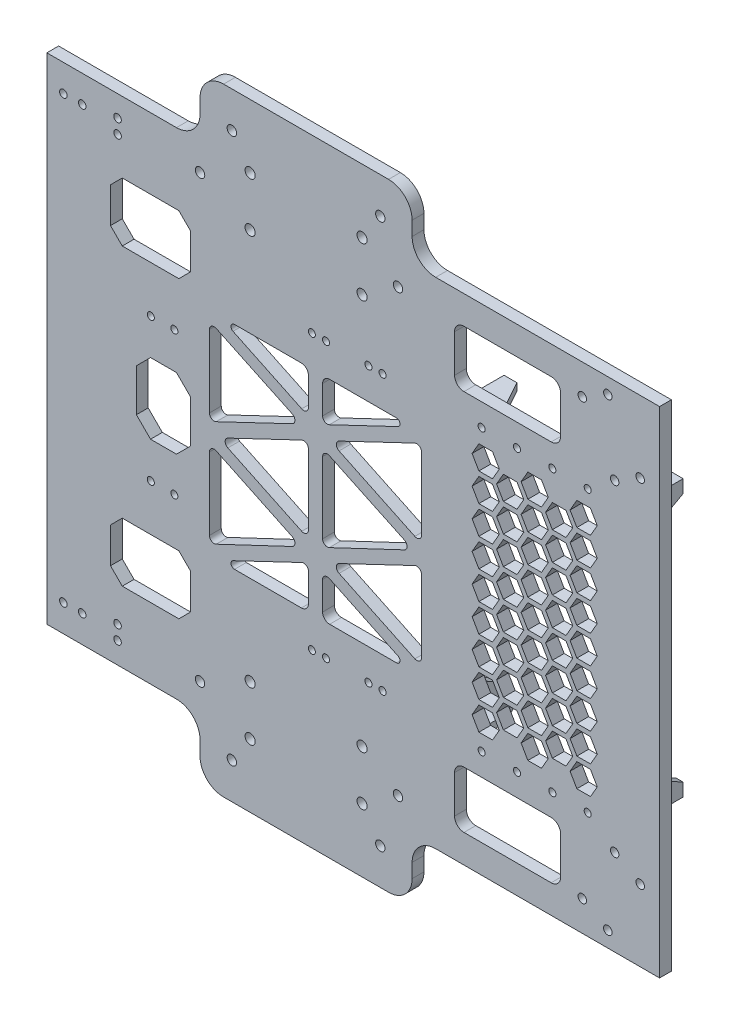
SolidWorks part; units mm, degrees
ref_plane "前视基准面" through (0, 0, 0) normal (0, 0, 1) x (1, 0, 0)
ref_plane "上视基准面" through (0, 0, 0) normal (0, 1, 0) x (1, 0, 0)
ref_plane "右视基准面" through (0, 0, 0) normal (1, 0, 0) x (0, 0, -1)
sketch "草图1" plane through (0, 0, 0) normal (0, 0, 1) x (1, 0, 0)
  line L2 (-130, 105) -> (-130, -105)
  line L3 (-130, -105) -> (-75, -105)
  line L4 (130, 95) -> (130, -95)
  line L5 (126.7518, 102.3765) -> (130, 105) construction
  line L9 (-65, -115) -> (-65, -121)
  line L10 (-55, -131) -> (15, -131)
  line L11 (25, -121) -> (25, -115)
  line L13 (35, -105) -> (120, -105)
  line L14 (126.7518, -102.3765) -> (130, -105) construction
  line L16 (-130, 0) -> (130, 0) construction
  line L17 (35, 105) -> (120, 105)
  line L18 (25, 121) -> (25, 115)
  line L19 (-55, 131) -> (15, 131)
  line L20 (-65, 115) -> (-65, 121)
  line L21 (-130, 105) -> (-75, 105)
  arc A3 (120, -105) -> (130, -95) centre (120, -95) ccw
  arc A8 (-65, -115) -> (-75, -105) centre (-75, -115) ccw
  arc A9 (25, -115) -> (35, -105) centre (35, -115) cw
  arc A10 (-55, -131) -> (-65, -121) centre (-55, -121) cw
  arc A11 (15, -131) -> (25, -121) centre (15, -121) ccw
  arc A12 (15, 131) -> (25, 121) centre (15, 121) cw
  arc A13 (-55, 131) -> (-65, 121) centre (-55, 121) ccw
  arc A14 (25, 115) -> (35, 105) centre (35, 115) ccw
  arc A15 (-65, 115) -> (-75, 105) centre (-75, 115) cw
  arc A16 (120, 105) -> (130, 95) centre (120, 95) cw
  point P0 (0, 0)
  point P40 (25, -105)
  point P45 (25, 105)
  dimension "D3" = 65
  dimension "D4" = 10
  dimension "D5" = 105
  dimension "D7" = 10
  dimension "D8" = 10
  dimension "D10" = 10
  dimension "D12" = 10
  dimension "D13" = 105
  dimension "D18" = 90
  dimension "D19" = 6
extrude "凸台-拉伸1" add sketch "草图1" along normal blind 5
sketch "草图4" plane through (0, 0, 0) normal (0, 0, -1) x (-1, 0, 0)
  line L0 (-39, -47.5) -> (-39, -58.5)
  line L1 (-39, -58.5) -> (-50, -58.5)
  line L2 (-50, -58.5) -> (-50, -55.5)
  line L3 (-50, -55.5) -> (-42, -55.5)
  line L4 (-42, -55.5) -> (-42, -47.5)
  line L5 (-42, -47.5) -> (-39, -47.5)
  line L6 (-130, 0) -> (-25.5592, 0) construction
  line L7 (-130, -95) -> (-130, 95) construction
  line L10 (-130, -95) -> (-130, 95) construction
  dimension "D1" = 11
  dimension "D2" = 11
  dimension "D3" = 3
  dimension "D4" = 3
  dimension "D5" = 80
  dimension "D7" = 55.5
extrude "凸台-拉伸2" add sketch "草图4" along normal blind 20
sketch "草图5" plane through (0, -58.5, 0) normal (0, -1, 0) x (1, 0, 0)
  line L0 (50, -10) -> (44.5, -20)
  line L1 (50, -20) -> (50, 0) construction
  line L2 (50, -20) -> (39, -20) construction
  line L3 (44.5, -20) -> (50, -20)
  line L4 (50, -20) -> (50, -10)
  dimension "D1" = 10
  dimension "D2" = 5.5
extrude "切除-拉伸3" cut sketch "草图5" against normal blind 10
sketch "草图6" plane through (39, 0, 0) normal (-1, 0, 0) x (0, 0, 1)
  line L0 (-20, -53) -> (-10, -47.5)
  line L1 (-20, -58.5) -> (-20, -47.5) construction
  line L2 (-20, -47.5) -> (0, -47.5) construction
  line L3 (-10, -47.5) -> (-20, -47.5)
  line L4 (-20, -47.5) -> (-20, -53)
  dimension "D1" = 10
  dimension "D2" = 5.5
extrude "切除-拉伸4" cut sketch "草图6" against normal blind 10
ref_plane "基准面2" through (77, 0, 0) normal (1, 0, 0) x (0, 0, -1)
mirror "镜向1" about plane through (77, 0, 0) normal (1, 0, 0) of "凸台-拉伸2", "切除-拉伸4", "切除-拉伸3"
mirror "镜向2" about plane through (0, 0, 0) normal (0, 1, 0) of "镜向1"
sketch "草图7" plane through (0, 0, 0) normal (0, 0, -1) x (-1, 0, 0)
  line L4 (-112, -55.5) -> (-104, -55.5) construction
  line L5 (-112, 47.5) -> (-112, 55.5) construction
  line L6 (-112, 55.5) -> (-104, 55.5) construction
  line L7 (-92.013, 36) -> (-94.8997, 41)
  line L8 (-94.8997, 41) -> (-100.6732, 41)
  line L9 (-100.6732, 41) -> (-103.56, 36)
  line L10 (-103.56, 36) -> (-100.6732, 31)
  line L11 (-100.6732, 31) -> (-94.8997, 31)
  line L12 (-94.8997, 31) -> (-92.013, 36)
  line L13 (-77.0019, 36) -> (-97.7865, 36) construction
  line L14 (-74.1151, 31) -> (-71.2284, 36)
  line L15 (-71.2284, 36) -> (-74.1151, 41)
  line L16 (-74.1151, 41) -> (-79.8886, 41)
  line L17 (-79.8886, 41) -> (-82.7754, 36)
  line L18 (-82.7754, 36) -> (-79.8886, 31)
  line L19 (-79.8886, 31) -> (-74.1151, 31)
  line L20 (-92.013, 24) -> (-94.8997, 29)
  line L21 (-93.1677, 30) -> (-90.2809, 25)
  line L22 (-90.2809, 25) -> (-84.5074, 25)
  line L23 (-84.5074, 25) -> (-81.6207, 30)
  line L24 (-81.6207, 30) -> (-84.5074, 35)
  line L25 (-84.5074, 35) -> (-90.2809, 35)
  line L26 (-90.2809, 35) -> (-93.1677, 30)
  line L27 (-84.5074, 37) -> (-81.6207, 42)
  line L28 (-81.6207, 42) -> (-84.5074, 47)
  line L29 (-84.5074, 47) -> (-90.2809, 47)
  line L30 (-90.2809, 47) -> (-93.1677, 42)
  line L31 (-93.1677, 42) -> (-90.2809, 37)
  line L32 (-90.2809, 37) -> (-84.5074, 37)
  line L33 (-79.8886, 43) -> (-74.1151, 43)
  line L34 (-74.1151, 43) -> (-71.2284, 48)
  line L35 (-71.2284, 48) -> (-74.1151, 53)
  line L36 (-74.1151, 53) -> (-79.8886, 53)
  line L37 (-79.8886, 53) -> (-82.7754, 48)
  line L38 (-82.7754, 48) -> (-79.8886, 43)
  line L39 (-94.8997, 43) -> (-92.013, 48)
  line L40 (-92.013, 48) -> (-94.8997, 53)
  line L41 (-94.8997, 53) -> (-100.6732, 53)
  line L42 (-100.6732, 53) -> (-103.56, 48)
  line L43 (-103.56, 48) -> (-100.6732, 43)
  line L44 (-100.6732, 43) -> (-94.8997, 43)
  line L45 (-72.3831, 42) -> (-69.4963, 37)
  line L46 (-69.4963, 37) -> (-63.7228, 37)
  line L47 (-63.7228, 37) -> (-60.8361, 42)
  line L48 (-60.8361, 42) -> (-63.7228, 47)
  line L49 (-63.7228, 47) -> (-69.4963, 47)
  line L50 (-69.4963, 47) -> (-72.3831, 42)
  line L51 (-94.8997, 29) -> (-100.6732, 29)
  line L52 (-100.6732, 29) -> (-103.56, 24)
  line L53 (-103.56, 24) -> (-100.6732, 19)
  line L54 (-100.6732, 19) -> (-94.8997, 19)
  line L55 (-94.8997, 19) -> (-92.013, 24)
  line L56 (-93.1677, 18) -> (-90.2809, 13)
  line L57 (-90.2809, 13) -> (-84.5074, 13)
  line L58 (-84.5074, 13) -> (-81.6207, 18)
  line L59 (-81.6207, 18) -> (-84.5074, 23)
  line L60 (-84.5074, 23) -> (-90.2809, 23)
  line L61 (-90.2809, 23) -> (-93.1677, 18)
  line L62 (-74.1151, 19) -> (-71.2284, 24)
  line L63 (-71.2284, 24) -> (-74.1151, 29)
  line L64 (-74.1151, 29) -> (-79.8886, 29)
  line L65 (-79.8886, 29) -> (-82.7754, 24)
  line L66 (-82.7754, 24) -> (-79.8886, 19)
  line L67 (-79.8886, 19) -> (-74.1151, 19)
  line L68 (-72.3831, 30) -> (-69.4963, 25)
  line L69 (-69.4963, 25) -> (-63.7228, 25)
  line L70 (-63.7228, 25) -> (-60.8361, 30)
  line L71 (-60.8361, 30) -> (-63.7228, 35)
  line L72 (-63.7228, 35) -> (-69.4963, 35)
  line L73 (-69.4963, 35) -> (-72.3831, 30)
  line L74 (-92.013, 12) -> (-94.8997, 17)
  line L75 (-94.8997, 17) -> (-100.6732, 17)
  line L76 (-100.6732, 17) -> (-103.56, 12)
  line L77 (-103.56, 12) -> (-100.6732, 7)
  line L78 (-100.6732, 7) -> (-94.8997, 7)
  line L79 (-94.8997, 7) -> (-92.013, 12)
  line L80 (-93.1677, 6) -> (-90.2809, 1)
  line L81 (-90.2809, 1) -> (-84.5074, 1)
  line L82 (-84.5074, 1) -> (-81.6207, 6)
  line L83 (-81.6207, 6) -> (-84.5074, 11)
  line L84 (-84.5074, 11) -> (-90.2809, 11)
  line L85 (-90.2809, 11) -> (-93.1677, 6)
  line L86 (-74.1151, 7) -> (-71.2284, 12)
  line L87 (-71.2284, 12) -> (-74.1151, 17)
  line L88 (-74.1151, 17) -> (-79.8886, 17)
  line L89 (-79.8886, 17) -> (-82.7754, 12)
  line L90 (-82.7754, 12) -> (-79.8886, 7)
  line L91 (-79.8886, 7) -> (-74.1151, 7)
  line L92 (-72.3831, 18) -> (-69.4963, 13)
  line L93 (-69.4963, 13) -> (-63.7228, 13)
  line L94 (-63.7228, 13) -> (-60.8361, 18)
  line L95 (-60.8361, 18) -> (-63.7228, 23)
  line L96 (-63.7228, 23) -> (-69.4963, 23)
  line L97 (-69.4963, 23) -> (-72.3831, 18)
  line L98 (-92.013, 0) -> (-94.8997, 5)
  line L99 (-94.8997, 5) -> (-100.6732, 5)
  line L100 (-100.6732, 5) -> (-103.56, 0)
  line L101 (-103.56, 0) -> (-100.6732, -5)
  line L102 (-100.6732, -5) -> (-94.8997, -5)
  line L103 (-94.8997, -5) -> (-92.013, 0)
  line L104 (-93.1677, -6) -> (-90.2809, -11)
  line L105 (-90.2809, -11) -> (-84.5074, -11)
  line L106 (-84.5074, -11) -> (-81.6207, -6)
  line L107 (-81.6207, -6) -> (-84.5074, -1)
  line L108 (-84.5074, -1) -> (-90.2809, -1)
  line L109 (-90.2809, -1) -> (-93.1677, -6)
  line L110 (-74.1151, -5) -> (-71.2284, 0)
  line L111 (-71.2284, 0) -> (-74.1151, 5)
  line L112 (-74.1151, 5) -> (-79.8886, 5)
  line L113 (-79.8886, 5) -> (-82.7754, 0)
  line L114 (-82.7754, 0) -> (-79.8886, -5)
  line L115 (-79.8886, -5) -> (-74.1151, -5)
  line L116 (-72.3831, 6) -> (-69.4963, 1)
  line L117 (-69.4963, 1) -> (-63.7228, 1)
  line L118 (-63.7228, 1) -> (-60.8361, 6)
  line L119 (-60.8361, 6) -> (-63.7228, 11)
  line L120 (-63.7228, 11) -> (-69.4963, 11)
  line L121 (-69.4963, 11) -> (-72.3831, 6)
  line L122 (-92.013, -12) -> (-94.8997, -7)
  line L123 (-94.8997, -7) -> (-100.6732, -7)
  line L124 (-100.6732, -7) -> (-103.56, -12)
  line L125 (-103.56, -12) -> (-100.6732, -17)
  line L126 (-100.6732, -17) -> (-94.8997, -17)
  line L127 (-94.8997, -17) -> (-92.013, -12)
  line L128 (-93.1677, -18) -> (-90.2809, -23)
  line L129 (-90.2809, -23) -> (-84.5074, -23)
  line L130 (-84.5074, -23) -> (-81.6207, -18)
  line L131 (-81.6207, -18) -> (-84.5074, -13)
  line L132 (-84.5074, -13) -> (-90.2809, -13)
  line L133 (-90.2809, -13) -> (-93.1677, -18)
  line L134 (-74.1151, -17) -> (-71.2284, -12)
  line L135 (-71.2284, -12) -> (-74.1151, -7)
  line L136 (-74.1151, -7) -> (-79.8886, -7)
  line L137 (-79.8886, -7) -> (-82.7754, -12)
  line L138 (-82.7754, -12) -> (-79.8886, -17)
  line L139 (-79.8886, -17) -> (-74.1151, -17)
  line L140 (-72.3831, -6) -> (-69.4963, -11)
  line L141 (-69.4963, -11) -> (-63.7228, -11)
  line L142 (-63.7228, -11) -> (-60.8361, -6)
  line L143 (-60.8361, -6) -> (-63.7228, -1)
  line L144 (-63.7228, -1) -> (-69.4963, -1)
  line L145 (-69.4963, -1) -> (-72.3831, -6)
  line L146 (-92.013, -24) -> (-94.8997, -19)
  line L147 (-94.8997, -19) -> (-100.6732, -19)
  line L148 (-100.6732, -19) -> (-103.56, -24)
  line L149 (-103.56, -24) -> (-100.6732, -29)
  line L150 (-100.6732, -29) -> (-94.8997, -29)
  line L151 (-94.8997, -29) -> (-92.013, -24)
  line L152 (-93.1677, -30) -> (-90.2809, -35)
  line L153 (-90.2809, -35) -> (-84.5074, -35)
  line L154 (-84.5074, -35) -> (-81.6207, -30)
  line L155 (-81.6207, -30) -> (-84.5074, -25)
  line L156 (-84.5074, -25) -> (-90.2809, -25)
  line L157 (-90.2809, -25) -> (-93.1677, -30)
  line L158 (-74.1151, -29) -> (-71.2284, -24)
  line L159 (-71.2284, -24) -> (-74.1151, -19)
  line L160 (-74.1151, -19) -> (-79.8886, -19)
  line L161 (-79.8886, -19) -> (-82.7754, -24)
  line L162 (-82.7754, -24) -> (-79.8886, -29)
  line L163 (-79.8886, -29) -> (-74.1151, -29)
  line L164 (-72.3831, -18) -> (-69.4963, -23)
  line L165 (-69.4963, -23) -> (-63.7228, -23)
  line L166 (-63.7228, -23) -> (-60.8361, -18)
  line L167 (-60.8361, -18) -> (-63.7228, -13)
  line L168 (-63.7228, -13) -> (-69.4963, -13)
  line L169 (-69.4963, -13) -> (-72.3831, -18)
  line L170 (-92.013, -36) -> (-94.8997, -31)
  line L171 (-94.8997, -31) -> (-100.6732, -31)
  line L172 (-100.6732, -31) -> (-103.56, -36)
  line L173 (-103.56, -36) -> (-100.6732, -41)
  line L174 (-100.6732, -41) -> (-94.8997, -41)
  line L175 (-94.8997, -41) -> (-92.013, -36)
  line L176 (-93.1677, -42) -> (-90.2809, -47)
  line L177 (-90.2809, -47) -> (-84.5074, -47)
  line L178 (-84.5074, -47) -> (-81.6207, -42)
  line L179 (-81.6207, -42) -> (-84.5074, -37)
  line L180 (-84.5074, -37) -> (-90.2809, -37)
  line L181 (-90.2809, -37) -> (-93.1677, -42)
  line L182 (-74.1151, -41) -> (-71.2284, -36)
  line L183 (-71.2284, -36) -> (-74.1151, -31)
  line L184 (-74.1151, -31) -> (-79.8886, -31)
  line L185 (-79.8886, -31) -> (-82.7754, -36)
  line L186 (-82.7754, -36) -> (-79.8886, -41)
  line L187 (-79.8886, -41) -> (-74.1151, -41)
  line L188 (-72.3831, -30) -> (-69.4963, -35)
  line L189 (-69.4963, -35) -> (-63.7228, -35)
  line L190 (-63.7228, -35) -> (-60.8361, -30)
  line L191 (-60.8361, -30) -> (-63.7228, -25)
  line L192 (-63.7228, -25) -> (-69.4963, -25)
  line L193 (-69.4963, -25) -> (-72.3831, -30)
  line L194 (-92.013, -48) -> (-94.8997, -43)
  line L195 (-94.8997, -43) -> (-100.6732, -43)
  line L196 (-100.6732, -43) -> (-103.56, -48)
  line L197 (-103.56, -48) -> (-100.6732, -53)
  line L198 (-100.6732, -53) -> (-94.8997, -53)
  line L199 (-94.8997, -53) -> (-92.013, -48)
  line L206 (-74.1151, -53) -> (-71.2284, -48)
  line L207 (-71.2284, -48) -> (-74.1151, -43)
  line L208 (-74.1151, -43) -> (-79.8886, -43)
  line L209 (-79.8886, -43) -> (-82.7754, -48)
  line L210 (-82.7754, -48) -> (-79.8886, -53)
  line L211 (-79.8886, -53) -> (-74.1151, -53)
  line L212 (-72.3831, -42) -> (-69.4963, -47)
  line L213 (-69.4963, -47) -> (-63.7228, -47)
  line L214 (-63.7228, -47) -> (-60.8361, -42)
  line L215 (-60.8361, -42) -> (-63.7228, -37)
  line L216 (-63.7228, -37) -> (-69.4963, -37)
  line L217 (-69.4963, -37) -> (-72.3831, -42)
  line L218 (-61.9908, 36) -> (-59.104, 31)
  line L219 (-61.9908, 48) -> (-59.104, 43)
  line L220 (-59.104, 43) -> (-53.3305, 43)
  line L221 (-53.3305, 43) -> (-50.4438, 48)
  line L222 (-50.4438, 48) -> (-53.3305, 53)
  line L223 (-53.3305, 53) -> (-59.104, 53)
  line L224 (-59.104, 53) -> (-61.9908, 48)
  line L225 (-59.104, 31) -> (-53.3305, 31)
  line L226 (-53.3305, 31) -> (-50.4438, 36)
  line L227 (-50.4438, 36) -> (-53.3305, 41)
  line L228 (-53.3305, 41) -> (-59.104, 41)
  line L229 (-59.104, 41) -> (-61.9908, 36)
  line L230 (-61.9908, 24) -> (-59.104, 19)
  line L231 (-59.104, 19) -> (-53.3305, 19)
  line L232 (-53.3305, 19) -> (-50.4438, 24)
  line L233 (-50.4438, 24) -> (-53.3305, 29)
  line L234 (-53.3305, 29) -> (-59.104, 29)
  line L235 (-59.104, 29) -> (-61.9908, 24)
  line L236 (-61.9908, 12) -> (-59.104, 7)
  line L237 (-59.104, 7) -> (-53.3305, 7)
  line L238 (-53.3305, 7) -> (-50.4438, 12)
  line L239 (-50.4438, 12) -> (-53.3305, 17)
  line L240 (-53.3305, 17) -> (-59.104, 17)
  line L241 (-59.104, 17) -> (-61.9908, 12)
  line L242 (-61.9908, 0) -> (-59.104, -5)
  line L243 (-59.104, -5) -> (-53.3305, -5)
  line L244 (-53.3305, -5) -> (-50.4438, 0)
  line L245 (-50.4438, 0) -> (-53.3305, 5)
  line L246 (-53.3305, 5) -> (-59.104, 5)
  line L247 (-59.104, 5) -> (-61.9908, 0)
  line L248 (-61.9908, -12) -> (-59.104, -17)
  line L249 (-59.104, -17) -> (-53.3305, -17)
  line L250 (-53.3305, -17) -> (-50.4438, -12)
  line L251 (-50.4438, -12) -> (-53.3305, -7)
  line L252 (-53.3305, -7) -> (-59.104, -7)
  line L253 (-59.104, -7) -> (-61.9908, -12)
  line L254 (-61.9908, -24) -> (-59.104, -29)
  line L255 (-59.104, -29) -> (-53.3305, -29)
  line L256 (-53.3305, -29) -> (-50.4438, -24)
  line L257 (-50.4438, -24) -> (-53.3305, -19)
  line L258 (-53.3305, -19) -> (-59.104, -19)
  line L259 (-59.104, -19) -> (-61.9908, -24)
  line L260 (-61.9908, -36) -> (-59.104, -41)
  line L261 (-59.104, -41) -> (-53.3305, -41)
  line L262 (-53.3305, -41) -> (-50.4438, -36)
  line L263 (-50.4438, -36) -> (-53.3305, -31)
  line L264 (-53.3305, -31) -> (-59.104, -31)
  line L265 (-59.104, -31) -> (-61.9908, -36)
  line L266 (-61.9908, -48) -> (-59.104, -53)
  line L267 (-59.104, -53) -> (-53.3305, -53)
  line L268 (-53.3305, -53) -> (-50.4438, -48)
  line L269 (-50.4438, -48) -> (-53.3305, -43)
  line L270 (-53.3305, -43) -> (-59.104, -43)
  line L271 (-59.104, -43) -> (-61.9908, -48)
  line L272 (-93.1677, -54) -> (-90.2809, -59) [skipped]
  line L273 (-90.2809, -59) -> (-84.5074, -59) [skipped]
  line L274 (-84.5074, -59) -> (-81.6207, -54) [skipped]
  line L275 (-81.6207, -54) -> (-84.5074, -49) [skipped]
  line L276 (-84.5074, -49) -> (-90.2809, -49) [skipped]
  line L277 (-90.2809, -49) -> (-93.1677, -54) [skipped]
  circle A0 centre (-97.7865, 36) radius 5 construction
  circle A1 centre (-77.0019, 36) radius 5 construction
  circle A2 centre (-87.3942, 30) radius 5 construction
  circle A3 centre (-87.3942, 42) radius 5 construction
  circle A4 centre (-77.0019, 48) radius 5 construction
  circle A5 centre (-97.7865, 48) radius 5 construction
  circle A6 centre (-66.6096, 42) radius 5 construction
  circle A7 centre (-56.2173, 48) radius 5 construction
  point P4 (-87.3942, 37)
  dimension "D1" = 2
  dimension "D3" = 10
  dimension "D4" = 10
  dimension "D5" = 2
  dimension "D7" = 10
  dimension "D11" = 10
  dimension "D14" = 10
  dimension "D15" = 10
  dimension "D20" = 10
  dimension "D2" = 2
  dimension "D6" = 2
  dimension "D8" = 2
  dimension "D9" = 2
  dimension "D10" = 2
  dimension "D12" = 2
  dimension "D13" = 2
  dimension "D16" = 2
  dimension "D17" = 2
  dimension "D19" = 2
  dimension "D21" = 9
  dimension "D22" = 2.5
  dimension "D23" = 2.5
  dimension "D24" = 8.44
  dimension "D18" = 8
extrude "切除-拉伸5" cut sketch "草图7" against normal blind 5
sketch "草图8" plane through (0, 0, 0) normal (0, 0, -1) x (-1, 0, 0)
  line L0 (-75.3677, 120) -> (-75.3677, -120)
  line L1 (-100.0285, 77.2863) -> (-100.0285, -77.2863)
  line L2 (-100.0285, 77.2863) -> (-75.3677, 120)
  line L3 (-100.0285, -77.2863) -> (-75.3677, -120)
  line L4 (-37.1297, 0) -> (-146.8562, 0) construction
  dimension "D1" = 30
  dimension "D2" = 30
  dimension "D3" = 120
  dimension "D4" = 120
sketch "草图9" plane through (0, 0, 0) normal (0, 0, -1) x (-1, 0, 0)
  line L0 (148.8518, 0) -> (-37.1297, 0) construction
  line L1 (-29, 41) -> (-29, 4)
  line L2 (-25, -45) -> (13, -45)
  line L3 (61, -41) -> (61, -4)
  line L4 (57, 45) -> (19, 45)
  line L14 (-29, 41) -> (9.8049, 22.5)
  line L15 (57, 0) -> (19, -18.1163)
  line L16 (130, 105) -> (130, -105) construction
  line L17 (63, 93) -> (118, 93)
  line L18 (63, 93) -> (63, 66)
  line L19 (63, 66) -> (118, 66)
  line L20 (118, 93) -> (118, 66)
  line L21 (75, 105) -> (130, 105) construction
  line L22 (63, -66) -> (118, -66)
  line L23 (118, -93) -> (118, -66)
  line L24 (63, -93) -> (118, -93)
  line L25 (63, -93) -> (63, -66)
  line L26 (-120, 105) -> (-35, 105) construction
  line L27 (-43, 93) -> (-88, 93)
  line L28 (-43, 93) -> (-43, 69)
  line L29 (-43, 69) -> (-88, 69)
  line L30 (-88, 93) -> (-88, 69)
  line L31 (-130, -95) -> (-130, 95) construction
  line L32 (-43, -69) -> (-88, -69)
  line L33 (-88, -93) -> (-88, -69)
  line L34 (-43, -93) -> (-88, -93)
  line L35 (-43, -93) -> (-43, -69)
  line L36 (-25, 45) -> (13, 26.8837)
  line L37 (-25, -45) -> (13, -26.8837)
  line L38 (61, 41) -> (22.0746, 22.5575)
  line L39 (-25.5359, 0) -> (13, -18.258)
  line L40 (57, 45) -> (19, 26.8837)
  line L41 (57, -45) -> (19, -26.8837)
  line L42 (16, 61.4977) -> (16, -60.5731) construction
  line L43 (13, 45) -> (13, 26.8837)
  line L44 (19, 45) -> (19, 26.8837)
  line L45 (13, 18.258) -> (13, -18.258)
  line L46 (9.8049, 22.5) -> (-29, 4)
  line L47 (19, 18.1163) -> (57, 0)
  line L48 (22.0746, 22.5575) -> (61, 4)
  line L49 (13, 18.258) -> (-25.5359, 0)
  line L50 (19, 18.1163) -> (19, -18.1163)
  line L51 (22.0746, -22.5575) -> (61, -41)
  line L52 (9.8049, -22.5) -> (-29, -41)
  line L53 (9.8049, -22.5) -> (-29, -4)
  line L54 (22.0746, -22.5575) -> (61, -4)
  line L55 (13, -26.8837) -> (13, -45)
  line L56 (19, -26.8837) -> (19, -45)
  line L57 (13, 45) -> (-25, 45)
  line L58 (-29, -4) -> (-29, -41)
  line L59 (19, -45) -> (57, -45)
  line L60 (61, 4) -> (61, 41)
  line L61 (-44, 41) -> (-44, -37.8122) construction
  dimension "D1" = 45
  dimension "D2" = 45
  dimension "D3" = 15
  dimension "D4" = 90
  dimension "D5" = 1
  dimension "D7" = 12
  dimension "D8" = 12
  dimension "D9" = 27
  dimension "D10" = 55
  dimension "D11" = 12
  dimension "D12" = 45
  dimension "D13" = 42
  dimension "D14" = 24
  dimension "D21" = 4
  dimension "D22" = 4
  dimension "D23" = 4
  dimension "D24" = 4
  dimension "D26" = 4
  dimension "D27" = 3
  dimension "D28" = 45
extrude "切除-拉伸6" cut sketch "草图9" against normal blind 5 contours L27 L30 L29 L28 | L34 L35 L32 L33 | L4 L44 L40 | L48 L60 L38 | L47 L50 L15 | L54 L51 L3 | L56 L59 L41 | L55 L37 L2 | L53 L58 L52 | L45 L49 L39 | L46 L14 L1 | L43 L57 L36 | L57 L36 L43 region at (16.065, 22.5, 0) region at (-0.3333, -38.9612, 0) region at (-48.0249, -22.5192, 0) region at (-31.6667, 38.9612, 0) region at (-31.6667, 0, 0) region at (65.5, 81, 0) region at (65.5, -81, 0) region at (-0.3333, 38.9612, 0) region at (-48.0249, 22.5192, 0) region at (-0.1547, 0, 0) region at (-31.6667, -38.9612, 0) region at (16.065, -22.5, 0)
fillet "圆角1" radius 4 8 edges at (43, -93, 2.5) (88, -69, 2.5) (43, -69, 2.5) (88, -93, 2.5) (88, 69, 2.5) (43, 69, 2.5) (43, 93, 2.5) (88, 93, 2.5)
fillet "圆角2" radius 1.5 4 edges at (25, -45, 2.5) (-57, -45, 2.5) (25, 45, 2.5) (-57, 45, 2.5)
fillet "圆角3" radius 2 22 edges at (29, -4, 2.5) (29, 4, 2.5) (-13, -18.258, 2.5) (-61, -41, 2.5) (-61, 4, 2.5) (-13, -26.8837, 2.5) (-13, 18.258, 2.5) (-61, -4, 2.5) (-22.0746, -22.5575, 2.5) (25.5359, 0, 2.5) (-22.0746, 22.5575, 2.5) (-61, 41, 2.5) (-19, 26.8837, 2.5) (-19, -26.8837, 2.5) (-19, -18.1163, 2.5) (29, -41, 2.5) (29, 41, 2.5) (-57, 0, 2.5) (-9.8049, -22.5, 2.5) (-13, 26.8837, 2.5) (-9.8049, 22.5, 2.5) (-19, 18.1163, 2.5)
fillet "圆角4" radius 3 4 edges at (-13, -45, 2.5) (-13, 45, 2.5) (-19, -45, 2.5) (-19, 45, 2.5)
sketch "草图12" plane through (0, 0, 0) normal (0, 0, -1) x (-1, 0, 0)
  line L1 (-120, 105) -> (-130, 105)
  line L2 (-120, 105) -> (-120, -105)
  line L3 (-120, -105) -> (-130, -105)
  line L4 (-130, 105) -> (-130, -105)
extrude "凸台-拉伸3" add sketch "草图12" against normal up to surface (5 mm away) up to face at (65.5, 81, 5)
hole_wizard "M3 六角头螺栓的柱形沉头孔1" positions "草图16" profile "草图17" counterbore size "M3" standard "GB" end condition through all
sketch "草图16" plane through (-124.3639, -131.0101, -4.2) normal (0, 0, -1) x (0, 1, 0)
  point P0 (221.0101, 24.3639)
  point P3 (227.0101, 24.3639)
sketch "草图17" plane through (-100, 90, -4.2) normal (1, 0, 0) x (0, 1, 0)
  line L0 (0, 0) -> (0, 9.2)
  line L1 (0, 9.2) -> (1.6, 9.2)
  line L2 (1.6, 9.2) -> (1.6, 1.6)
  line L3 (1.6, 1.6) -> (2.95, 1.6)
  line L4 (2.95, 1.6) -> (2.95, 0)
  line L5 (2.95, 0) -> (0, 0)
  line L6 (0, -6.35) -> (0, 107.95) construction
  dimension "通孔孔直径" = 3.2
  dimension "通孔孔深度" = 9.2
  dimension "柱形沉头孔直径" = 5.9
  dimension "柱形沉头孔深度" = 1.6
sketch "草图10" plane through (0, 0, 0) normal (0, 0, -1) x (-1, 0, 0)
  line L0 (-37.1297, 0) -> (-146.8562, 0) construction
  line L1 (-37.1297, 0) -> (-146.8562, 0) construction
  circle A0 centre (-121.782, 74.6081) radius 1.8 construction
  circle A1 centre (-110.9567, 68.3581) radius 1.8 construction
  circle A2 centre (-108.032, 98.4238) radius 1.8 construction
  circle A3 centre (-97.2067, 92.1738) radius 1.8 construction
  circle A4 centre (-3.75, 104) radius 2.15 construction
  circle A5 centre (-3.75, 104) radius 2.15
  circle A6 centre (-3.75, -104) radius 2.15
  circle A7 centre (115, 93.5) radius 1.6 construction
  circle A8 centre (123, 93.5) radius 1.6 construction
  circle A9 centre (115, 93.5) radius 1.6
  circle A10 centre (123, 93.5) radius 1.6
  circle A11 centre (123, -93.5) radius 1.6
  circle A12 centre (115, -93.5) radius 1.6
  circle A13 centre (100, 96) radius 1.6 construction
  circle A14 centre (100, 90) radius 1.6 construction
  circle A15 centre (-121.782, 74.6081) radius 1.8
  circle A16 centre (-110.9567, 68.3581) radius 1.8
  circle A17 centre (-108.032, 98.4238) radius 1.8
  circle A18 centre (-97.2067, 92.1738) radius 1.8
  circle A41 centre (-97.2067, -92.1738) radius 1.8
  circle A42 centre (-108.032, -98.4238) radius 1.8
  circle A43 centre (-110.9567, -68.3581) radius 1.8
  circle A44 centre (-121.782, -74.6081) radius 1.8
  circle A45 centre (-99.5, 59.5) radius 1.5 construction
  circle A46 centre (-84.5, 59.5) radius 1.5 construction
  circle A47 centre (-69.5, 59.5) radius 1.5 construction
  circle A48 centre (-54.5, 59.5) radius 1.5 construction
  circle A49 centre (-12.4571, 58.25) radius 1.5 construction
  circle A50 centre (-6.4571, 58.25) radius 1.5 construction
  circle A51 centre (11.5429, 58.25) radius 1.5 construction
  circle A52 centre (17.5429, 58.25) radius 1.5 construction
  circle A53 centre (-99.5, 59.5) radius 1.5
  circle A54 centre (-84.5, 59.5) radius 1.5
  circle A55 centre (-69.5, 59.5) radius 1.5
  circle A56 centre (-54.5, 59.5) radius 1.5
  circle A57 centre (-12.4571, 58.25) radius 1.5
  circle A58 centre (-6.4571, 58.25) radius 1.5
  circle A59 centre (11.5429, 58.25) radius 1.5
  circle A60 centre (17.5429, 58.25) radius 1.5
  circle A61 centre (17.5429, -58.25) radius 1.5
  circle A62 centre (11.5429, -58.25) radius 1.5
  circle A63 centre (-6.4571, -58.25) radius 1.5
  circle A64 centre (-12.4571, -58.25) radius 1.5
  circle A65 centre (-54.5, -59.5) radius 1.5
  circle A66 centre (-69.5, -59.5) radius 1.5
  circle A67 centre (-84.5, -59.5) radius 1.5
  circle A68 centre (-99.5, -59.5) radius 1.5
  circle A69 centre (100, 96) radius 1.6
  circle A70 centre (100, 90) radius 1.6
  circle A71 centre (100, -90) radius 1.6
  circle A72 centre (100, -96) radius 1.6
  circle A89 centre (75.897, 30.3) radius 1.5 construction
  circle A90 centre (85.897, 30.3) radius 1.5 construction
  circle A91 centre (75.897, 30.3) radius 1.5
  circle A92 centre (85.897, 30.3) radius 1.5
  circle A93 centre (85.897, -30.3) radius 1.5
  circle A94 centre (75.897, -30.3) radius 1.5
  circle A95 centre (43.75, 83) radius 2.15 construction
  circle A96 centre (43.75, 104) radius 2.15 construction
  circle A97 centre (-3.75, 83) radius 2.15 construction
  circle A99 centre (43.75, 83) radius 2.15
  circle A100 centre (43.75, 104) radius 2.15
  circle A101 centre (-3.75, 83) radius 2.15
  circle A104 centre (-3.75, -83) radius 2.15
  circle A105 centre (43.75, -104) radius 2.15
  circle A106 centre (43.75, -83) radius 2.15
extrude "切除-拉伸7" cut sketch "草图10" against normal through all
sketch "草图11" plane through (0, 0, 0) normal (0, 0, -1) x (-1, 0, 0)
  line L0 (130, 105) -> (130, -105) construction
  line L1 (74, -75) -> (98, -75)
  line L2 (69, -70) -> (69, -55)
  line L3 (74, -50) -> (98, -50)
  line L4 (103, -70) -> (103, -55)
  line L5 (130, 0) -> (108.529, 0) construction
  line L10 (69, -70) -> (74, -75)
  line L11 (69, -55) -> (74, -50)
  line L12 (98, -50) -> (103, -55)
  line L13 (98, -75) -> (103, -70)
  line L14 (98, 75) -> (103, 70)
  line L15 (98, 50) -> (103, 55)
  line L16 (69, 55) -> (74, 50)
  line L17 (69, 70) -> (74, 75)
  line L18 (103, 70) -> (103, 55)
  line L19 (74, 50) -> (98, 50)
  line L20 (69, 70) -> (69, 55)
  line L21 (74, 75) -> (98, 75)
  point P0 (69, -75)
  point P1 (103, -50)
  point P2 (69, -50)
  point P3 (103, -75)
  point P8 (103, 75)
  point P9 (69, 50)
  point P10 (103, 50)
  point P11 (69, 75)
  dimension "D1" = 34
  dimension "D2" = 25
  dimension "D3" = 27
  dimension "D4" = 50
extrude "切除-拉伸8" cut sketch "草图11" against normal through all
sketch "草图14" plane through (0, 0, 5) normal (0, 0, 1) x (1, 0, 0)
  line L0 (25, -121) -> (25, -115) construction
  line L1 (-55, -131) -> (15, -131) construction
  line L2 (-20, -131) -> (-20, 131) construction
  line L3 (15, 131) -> (-55, 131) construction
  line L4 (-20, 0) -> (-130, 0) construction
  line L5 (-130, 105) -> (-130, -105) construction
  circle A0 centre (11.5, -115.68) radius 2
  circle A1 centre (-51.5, -115.68) radius 2
  circle A2 centre (-51.5, 115.68) radius 2
  circle A3 centre (11.5, 115.68) radius 2
  dimension "D1" = 4
  dimension "D2" = 13.5
  dimension "D3" = 15.32
extrude "切除-拉伸9" cut sketch "草图14" against normal blind 10
sketch "草图15" plane through (0, 0, 0) normal (0, 0, -1) x (-1, 0, 0)
  line L0 (65, -93.5) -> (-19, -93.5) construction
  line L1 (130, 0) -> (-85.2757, 0) construction
  line L2 (130, 105) -> (130, -105) construction
  line L3 (-25, -121) -> (-25, -115) construction
  circle A0 centre (65, -93.5) radius 2
  circle A1 centre (-19, -93.5) radius 2
  circle A2 centre (65, 93.5) radius 2
  circle A3 centre (-19, 93.5) radius 2
  dimension "D1" = 4
  dimension "D3" = 6
  dimension "D2" = 84
extrude "切除-拉伸10" cut sketch "草图15" against normal through all
sketch "草图18" plane through (0, 0, 5) normal (0, 0, 1) x (1, 0, 0)
  line L0 (-130, 0) -> (-56.0355, 0) construction
  line L1 (-130, 105) -> (-130, -105) construction
  line L2 (-92, 9) -> (-86, 15)
  line L3 (-86, -15) -> (-75, -15)
  line L4 (-92, -9) -> (-92, 9)
  line L5 (-86, 15) -> (-75, 15)
  line L6 (-69, -9) -> (-69, 9)
  line L7 (-92, -15) -> (-69, 15) construction
  line L8 (-92, 15) -> (-69, -15) construction
  line L9 (-75, 15) -> (-69, 9)
  line L10 (-75, -15) -> (-69, -9)
  line L11 (-92, -9) -> (-86, -15)
  point P5 (-80.5, 0)
  dimension "D1" = 38
  dimension "D2" = 23
  dimension "D3" = 30
extrude "切除-拉伸11" cut sketch "草图18" against normal blind 10
equation "\"45、\"=43.7672"
